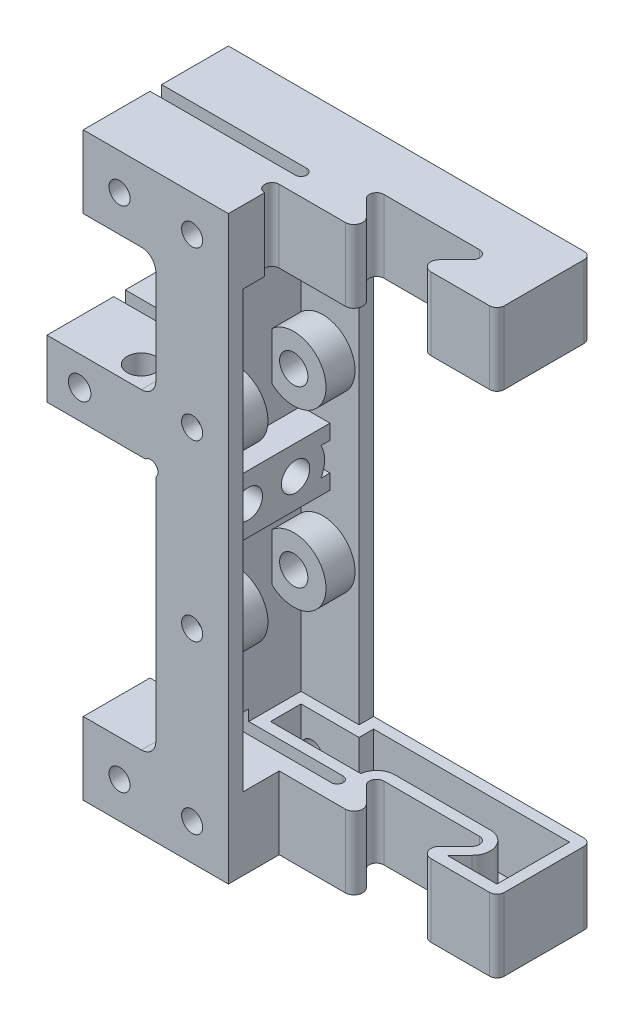
SolidWorks part; units mm, degrees
material "ABS"
ref_plane "Front Plane" through (0, 0, 0) normal (0, 0, 1) x (1, 0, 0)
ref_plane "Top Plane" through (0, 0, 0) normal (0, 1, 0) x (1, 0, 0)
ref_plane "Right Plane" through (0, 0, 0) normal (1, 0, 0) x (0, 0, -1)
sketch "Sketch1" plane through (0, 0, 0) normal (0, 0, 1) x (1, 0, 0)
  line L1 (10, -5) -> (-10, -5)
  line L2 (10, -5) -> (10, 5)
  line L3 (10, 5) -> (-10, 5)
  line L4 (-10, -5) -> (-10, 5)
  line L5 (10, -5) -> (-10, 5) construction
  line L6 (10, 5) -> (-10, -5) construction
  point P0 (0, 0)
  dimension "D1" = 20
  dimension "D2" = 10
extrude "Boss-Extrude1" add sketch "Sketch1" along normal blind 10 and the other way blind 10
hole_wizard "M2.5 Clearance Hole1" positions "Sketch3" profile "Sketch2" hole size "M2.5" standard "DIN" end condition through all
sketch "Sketch3" plane through (0, 0, 10) normal (0, 0, 1) x (1, 0, 0)
  line L7 (0, 0) -> (0, -3.6227) construction
  point P1 (-5, 0)
  point P5 (5, 0)
  dimension "D1" = 10
sketch "Sketch2" plane through (-5, 0, 10) normal (1, 0, 0) x (0, -1, 0)
  line L0 (0, 0) -> (0, 20.0001)
  line L1 (0, 20.0001) -> (1.45, 20.0001)
  line L2 (1.45, 20.0001) -> (1.45, 0)
  line L5 (1.45, 0) -> (0, 0)
  line L11 (0, -6.35) -> (0, 107.95) construction
  dimension "Thru Hole Dia." = 2.9
  dimension "Thru Hole Depth" = 20.0001
sketch "Sketch6" plane through (0, 0, 0) normal (0, 0, 1) x (1, 0, 0)
  line L0 (-10, -5) -> (10, -5) construction
  line L1 (10, -5) -> (0, -5)
  line L2 (10, -5) -> (10, -65)
  line L3 (10, -65) -> (0, -65)
  line L4 (0, -5) -> (0, -65)
  dimension "D1" = 60
extrude "Boss-Extrude2" add sketch "Sketch6" against normal up to surface and the other way up to surface up to face at (-3.55, 0, -10) other way up to face at (-3.55, 0, 10)
ref_plane "Plane1" through (0, -35, 0) normal (0, -1, 0) x (1, 0, 0)
mirror "Mirror1" about plane through (0, -35, 0) normal (0, -1, 0) of "M2.5 Clearance Hole1", "Boss-Extrude1"
sketch "Sketch4" plane through (0, 0, 0) normal (0, 0, 1) x (1, 0, 0)
  line L0 (-10, -5) -> (10, -5)
  line L1 (-10, 5) -> (10, 5)
  line L2 (-10, 5) -> (-10, -5)
  line L3 (-10, -75) -> (10, -75)
  line L4 (10, -75) -> (10, 5) construction
  line L5 (10, -75) -> (-10, -75) construction
  line L6 (-10, -65) -> (10, -65)
  line L7 (-10, -65) -> (-10, -75)
  line L8 (10, 5) -> (10, -5)
  line L9 (10, -75) -> (10, -65)
extrude "Cut-Extrude1" cut sketch "Sketch4" against normal blind 0.8 and the other way blind 0.8
sketch "Sketch7" plane through (0, 0, 0) normal (0, 0, 1) x (1, 0, 0)
  line L0 (0, -5) -> (0, -65) construction
  line L1 (0, -30) -> (-15, -30)
  line L2 (0, -30) -> (0, -22)
  line L3 (0, -22) -> (-15, -22)
  line L4 (-15, -30) -> (-15, -22)
  line L6 (0, -40) -> (-15, -40) construction
  line L7 (0, -40) -> (0, -48) construction
  line L8 (0, -48) -> (-15, -48) construction
  line L9 (-15, -40) -> (-15, -48) construction
  line L10 (-10, -5) -> (0, -5) construction
  dimension "D1" = 10
  dimension "D2" = 25
  dimension "D3" = 8
  dimension "D4" = 15
extrude "Boss-Extrude3" add sketch "Sketch7" along normal up to surface and the other way up to surface up to face at (-3.55, -70, 10) other way up to face at (-3.55, -70, -10)
sketch "Sketch8" plane through (10, 0, 0) normal (1, 0, 0) x (0, 0, -1)
  line L0 (10, 5) -> (-10, -75) construction
  line L1 (8, -65) -> (-8, -65)
  line L2 (8, -65) -> (8, -5)
  line L3 (8, -5) -> (-8, -5)
  line L4 (-8, -65) -> (-8, -5)
  line L5 (8, -65) -> (-8, -5) construction
  line L6 (8, -5) -> (-8, -65) construction
  line L7 (10, 5) -> (0.8, 5) construction
  line L8 (-10, -75) -> (-10, 5) construction
  point P0 (0, -35)
  dimension "D1" = 10
  dimension "D2" = 2
extrude "Cut-Extrude3" cut sketch "Sketch8" against normal blind 8
sketch "Sketch9" plane through (0, 0, 10) normal (0, 0, 1) x (1, 0, 0)
  line L0 (-0.7071, -30.7071) -> (0, -30) construction
  line L1 (-15, -30) -> (0, -30) construction
  line L2 (0, -30) -> (0, -65) construction
  line L3 (0, -30) -> (0, -65) construction
  line L4 (-15, -30) -> (0, -30) construction
  circle A0 centre (-0.7071, -30.7071) radius 1
  dimension "D1" = 2
extrude "Cut-Extrude4" cut sketch "Sketch9" against normal blind 35
fillet "Fillet1" radius 2 5 edges at (0, -22, 0)
sketch "Sketch11" plane through (0, -22, 0) normal (0, 1, 0) x (1, 0, 0)
  line L0 (0, 0) -> (-10, 0) construction
  line L1 (0, 10) -> (0, -10) construction
  line L3 (-5, 0) -> (-5, 7) construction
  circle A0 centre (-5, 7) radius 1.95
  circle A1 centre (-5, -7) radius 1.95
  dimension "D1" = 3.9
  dimension "D2" = 14
  dimension "D3" = 5
extrude "Cut-Extrude6" cut sketch "Sketch11" against normal blind 4
sketch "Sketch12" plane through (0, -22, 0) normal (0, 1, 0) x (1, 0, 0)
  circle A0 centre (-5, 7) radius 1.35
  circle A1 centre (-5, -7) radius 1.35
  dimension "D1" = 2.7
extrude "Cut-Extrude7" cut sketch "Sketch12" against normal blind 9
sketch "Sketch13" plane through (0, 0, 0) normal (-1, 0, 0) x (0, 0, 1)
  line L0 (0, 0) -> (0, -46.5773) construction
  line L1 (-10, -30) -> (10, -30) construction
  circle A0 centre (-3.25, -35) radius 1.35
  circle A1 centre (3.25, -35) radius 1.35
  dimension "D2" = 6.5
  dimension "D3" = 2.7
  dimension "D1" = 5
extrude "Cut-Extrude8" cut sketch "Sketch13" against normal blind 9
sketch "Sketch14" plane through (2, 0, 0) normal (1, 0, 0) x (0, 0, -1)
  circle A0 centre (-3.25, -35) radius 1.95
  circle A1 centre (3.25, -35) radius 1.95 construction
  circle A3 centre (-3.25, -35) radius 4
  dimension "D1" = 3.9
  dimension "D2" = 8
extrude "Boss-Extrude4" add sketch "Sketch14" along normal blind 4
mirror "Mirror2" about plane through (0, 0, 0) normal (0, 0, 1) of "Boss-Extrude4"
sketch "Sketch15" plane through (6, 0, 0) normal (1, 0, 0) x (0, 0, -1)
  line L0 (-8, -5) -> (-8, -65) construction
  line L1 (-8, -31) -> (8, -31)
  line L2 (-8, -31) -> (-8, -33.05)
  line L3 (-8, -33.05) -> (8, -33.05)
  line L4 (8, -31) -> (8, -33.05)
  line L5 (8, -65) -> (8, -5) construction
  line L6 (-3.25, -35) -> (11.9908, -35) construction
  line L7 (8, -39) -> (8, -36.95)
  line L8 (-8, -36.95) -> (8, -36.95)
  line L9 (-8, -39) -> (-8, -36.95)
  line L10 (-8, -39) -> (8, -39)
  circle A0 centre (3.25, -35) radius 1.95 construction
  arc A1 (0, -32.6682) -> (0, -37.3318) centre (-3.25, -35) ccw construction
extrude "Boss-Extrude5" add sketch "Sketch15" against normal up to surface (4 mm away) up to face at (2, -35, 0)
hole_wizard "M2.5 Clearance Hole2" positions "Sketch17" profile "Sketch16" hole size "M2.5" standard "DIN"
sketch "Sketch17" plane through (0, 0, -10) normal (0, 0, -1) x (-1, 0, 0)
  line L0 (-5, 0) -> (-5, -23) construction
  line L2 (-10, -35) -> (-30.659, -35) construction
  line L3 (-10, -75) -> (-10, 5) construction
  point P0 (-5, -23)
  point P17 (-5, -47)
  dimension "D1" = 23
sketch "Sketch16" plane through (5, -23, -10) normal (1, 0, 0) x (0, 1, 0)
  line L0 (0, 0) -> (0, 20)
  line L1 (0, 20) -> (1.45, 20)
  line L2 (1.45, 20) -> (1.45, 0)
  line L5 (1.45, 0) -> (0, 0)
  line L10 (0, 20) -> (-1.45, 20) construction
  line L11 (0, -6.35) -> (0, 107.95) construction
  dimension "Hole Dia." = 2.9
  dimension "Hole Depth" = 20
  dimension "Drill Angle" = 180
sketch "Sketch19" plane through (0, 0, 8) normal (0, 0, -1) x (-1, 0, 0)
  circle A0 centre (-5, -23) radius 1.95
  circle A1 centre (-5, -23) radius 4.45
  dimension "D1" = 3.9
  dimension "D2" = 2.5
extrude "Boss-Extrude6" add sketch "Sketch19" along normal blind 4
mirror "Mirror3" about plane through (0, 0, 0) normal (0, 0, 1) of "Boss-Extrude6"
ref_plane "Plane2" through (0, -35, 0) normal (0, 1, 0) x (-1, 0, 0)
mirror "Mirror4" about plane through (0, -35, 0) normal (0, 1, 0) of "Mirror3", "Boss-Extrude6"
sketch "Sketch20" plane through (0, 5, 0) normal (0, 1, 0) x (1, 0, 0)
  line L1 (-29.6046, 0.8) -> (0, 0.8)
  line L2 (-29.6046, 0.8) -> (-29.6046, -0.8)
  line L3 (-29.6046, -0.8) -> (0, -0.8)
  line L4 (0, 0.8) -> (0, -0.8)
  line L5 (10, -0.8) -> (-10, -0.8) construction
extrude "Cut-Extrude9" cut sketch "Sketch20" against normal blind 128
hole_wizard "M2.5 Clearance Hole3" positions "Sketch22" profile "Sketch23" hole size "M2.5" standard "DIN" end condition through all
sketch "Sketch22" plane through (0, 0, 10) normal (0, 0, 1) x (1, 0, 0)
  line L0 (-15, -26) -> (14.615, -26) construction
  line L1 (-15, -22) -> (-15, -30) construction
  point P0 (-10.5, -26)
  dimension "D1" = 4.5
sketch "Sketch23" plane through (-10.5, -26, 10) normal (1, 0, 0) x (0, -1, 0)
  line L0 (0, 0) -> (0, 20)
  line L1 (0, 20) -> (1.55, 20)
  line L2 (1.55, 20) -> (1.55, 0)
  line L5 (1.55, 0) -> (0, 0)
  line L11 (0, -6.35) -> (0, 107.95) construction
  dimension "Thru Hole Dia." = 3.1
  dimension "Thru Hole Depth" = 20
sketch "Sketch24" plane through (0, 0, 0) normal (-1, 0, 0) x (0, 0, 1)
  line L0 (-0.8, -5) -> (0.8, -5) construction
  line L1 (-0.8, -5) -> (0.8, -5)
  line L2 (-0.8, -5) -> (-0.8, -6.5)
  line L3 (-0.8, -6.5) -> (0.8, -6.5)
  line L4 (0.8, -5) -> (0.8, -6.5)
  line L5 (0.8, -7) -> (0.8, -5) construction
  line L6 (-0.8, -5) -> (-0.8, -7) construction
  line L7 (-10, 5) -> (-10, -75) construction
  line L8 (-10, -35) -> (15.2028, -35) construction
  line L9 (0.8, -65) -> (0.8, -63.5)
  line L10 (-0.8, -63.5) -> (0.8, -63.5)
  line L11 (-0.8, -65) -> (-0.8, -63.5)
  line L12 (-0.8, -65) -> (0.8, -65)
  dimension "D1" = 1.5
extrude "Cut-Extrude10" cut sketch "Sketch24" against normal blind 20
sketch "Sketch25" plane through (0, 5, 0) normal (0, 1, 0) x (1, 0, 0)
  line L0 (10, 10) -> (40, 10)
  line L1 (40, 10) -> (40, -3)
  line L2 (10, 10) -> (10, -3)
  line L3 (10, -3) -> (22, -3)
  line L4 (22, -3) -> (16, 3)
  line L5 (16, 3) -> (34, 3)
  line L6 (28, -3) -> (34, 3)
  line L7 (28, -3) -> (40, -3)
  line L8 (20.7373, 10) -> (40, 10) construction
  line L10 (10, 10) -> (10, 14.9089) construction
  line L11 (10, 10) -> (-10, 10) construction
  line L12 (10, 10) -> (10, 0.8) construction
  dimension "D1" = 45
extrude "Boss-Extrude7" add sketch "Sketch25" against normal blind 10
fillet "Fillet2" radius 1 4 edges at (34, 0, -3) (16, 0, -3) (40, 0, -10) (40, 0, 3)
fillet "Fillet3" radius 1.2 2 edges at (28, 0, 3) (22, 0, 3)
sketch "Sketch27" plane through (0, 5, 0) normal (0, 1, 0) x (1, 0, 0)
  line L0 (10, 0.8) -> (10, -0.8) construction
  line L1 (10, -3) -> (10, -10) construction
  circle A0 centre (10, 0) radius 0.8
  circle A1 centre (10, -4) radius 1
  dimension "D1" = 2
extrude "Cut-Extrude11" cut sketch "Sketch27" against normal blind 10
sketch "Sketch28" plane through (0, -5, 0) normal (0, -1, 0) x (1, 0, 0)
  line L0 (18.3787, 1.5) -> (11.7436, 1.5)
  line L1 (19.1029, 3) -> (10, 3) construction
  line L2 (18.3787, 1.5) -> (10, 1.5) construction
  line L5 (10, -2.3) -> (3.5, -2.3)
  line L6 (3.5, -2.3) -> (3.5, -6.5)
  line L7 (3.5, -6.5) -> (11.5, -6.5)
  line L8 (11.5, -6.5) -> (11.5, -8.5)
  line L9 (11.5, -8.5) -> (38.5, -8.5)
  line L10 (38.5, -8.5) -> (38.5, 1.5)
  line L11 (38.5, 1.5) -> (31.6213, 1.5)
  line L12 (31.6213, 1.5) -> (33.3536, -0.2322)
  line L13 (31.5858, -4.5) -> (18.4142, -4.5)
  line L14 (16.6464, -0.2322) -> (18.3787, 1.5)
  line L15 (19.1029, 3) -> (10, 3)
  line L16 (10, 5) -> (10, 8)
  line L17 (10, 8) -> (2, 8)
  line L18 (2, 8) -> (2, 0.8)
  line L19 (2, 0.8) -> (10, 0.8)
  line L20 (10, -0.8) -> (2, -0.8)
  line L21 (2, -0.8) -> (2, -8)
  line L22 (2, -8) -> (10, -8)
  line L23 (10, -8) -> (10, -10)
  line L24 (10, -10) -> (39, -10)
  line L25 (40, -9) -> (40, 2)
  line L26 (39, 3) -> (30.8971, 3)
  line L27 (30.0485, 0.9515) -> (32.2929, -1.2929)
  line L28 (31.5858, -3) -> (18.4142, -3)
  line L29 (17.7071, -1.2929) -> (19.9515, 0.9515)
  line L30 (19.1029, 3) -> (11.0887, 3) construction
  line L33 (2, 8) -> (2, 0.8) construction
  line L34 (2, 0.8) -> (10, 0.8) construction
  line L35 (10, -0.8) -> (2, -0.8) construction
  line L36 (2, -0.8) -> (2, -8) construction
  line L37 (2, -8) -> (10, -8) construction
  line L38 (10, -8) -> (10, -10) construction
  line L39 (10, -10) -> (39, -10) construction
  line L40 (40, -9) -> (40, 2) construction
  line L41 (39, 3) -> (30.8971, 3) construction
  line L42 (30.0485, 0.9515) -> (32.2929, -1.2929) construction
  line L43 (31.5858, -3) -> (18.4142, -3) construction
  line L44 (17.7071, -1.2929) -> (19.9515, 0.9515) construction
  line L45 (8.5, 6) -> (8.5, 6.5) construction
  line L46 (8.5, 6.5) -> (3.5, 6.5) construction
  line L47 (3.5, 6.5) -> (3.5, 2.3) construction
  line L48 (3.5, 2.3) -> (10, 2.3) construction
  line L49 (10, 5) -> (10, 8) construction
  line L50 (10, 8) -> (2, 8) construction
  arc A0 (10, -2.3) -> (10, 2.3) centre (10, 0) ccw construction
  arc A1 (10, -2.3) -> (11.7436, 1.5) centre (10, 0) ccw
  arc A2 (38.5, -8.5) -> (38.5, -8.5) centre (38.5, -8.5) ccw
  arc A3 (38.5, 1.5) -> (38.5, 1.5) centre (38.5, 1.5) ccw
  arc A4 (31.6213, 1.5) -> (31.6213, 1.5) centre (31.6213, 1.5) ccw
  arc A5 (31.5858, -4.5) -> (33.3536, -0.2322) centre (31.5858, -2) ccw
  arc A6 (16.6464, -0.2322) -> (18.4142, -4.5) centre (18.4142, -2) ccw
  arc A7 (18.3787, 1.5) -> (18.3787, 1.5) centre (18.3787, 1.5) ccw
  arc A8 (10, 5) -> (10, 3) centre (10, 4) ccw
  arc A9 (10, -0.8) -> (10, 0.8) centre (10, 0) ccw
  arc A10 (39, -10) -> (40, -9) centre (39, -9) ccw
  arc A11 (40, 2) -> (39, 3) centre (39, 2) ccw
  arc A12 (30.8971, 3) -> (30.0485, 0.9515) centre (30.8971, 1.8) ccw
  arc A13 (31.5858, -3) -> (32.2929, -1.2929) centre (31.5858, -2) ccw
  arc A14 (17.7071, -1.2929) -> (18.4142, -3) centre (18.4142, -2) ccw
  arc A17 (10, -0.8) -> (10, 0.8) centre (10, 0) ccw construction
  arc A18 (39, -10) -> (40, -9) centre (39, -9) ccw construction
  arc A19 (40, 2) -> (39, 3) centre (39, 2) ccw construction
  arc A20 (19.9515, 0.9515) -> (19.1029, 3) centre (19.1029, 1.8) ccw
  arc A21 (31.5858, -3) -> (32.2929, -1.2929) centre (31.5858, -2) ccw construction
  arc A22 (17.7071, -1.2929) -> (18.4142, -3) centre (18.4142, -2) ccw construction
  arc A24 (8.5, 6) -> (10, 1.5) centre (10, 4) ccw construction
  arc A25 (10, 5) -> (10, 3) centre (10, 4) ccw construction
  arc A33 (30.8971, 3) -> (30.0485, 0.9515) centre (30.5314, 1.9515) ccw construction
  arc A34 (19.9515, 0.9515) -> (19.1029, 3) centre (19.4686, 1.9515) ccw construction
  dimension "D1" = 0
  dimension "D2" = 1.5
extrude "Cut-Extrude12" cut sketch "Sketch28" against normal blind 8.5
ref_plane "Plane3" through (0, -35, 0) normal (0, 1, 0) x (-1, 0, 0)
mirror "Mirror5" about plane through (0, -35, 0) normal (0, 1, 0) of "Fillet3", "Fillet2", "Boss-Extrude7"
sketch "Sketch30" plane through (0, -75, 0) normal (0, -1, 0) x (1, 0, 0)
  line L1 (15, 0.8) -> (10, 0.8)
  line L2 (15, 0.8) -> (15, -0.8)
  line L3 (15, -0.8) -> (10, -0.8)
  line L4 (10, 0.8) -> (10, -0.8)
  line L5 (15, 0.8) -> (10, -0.8) construction
  line L6 (15, -0.8) -> (10, 0.8) construction
  point P0 (12.5, 0)
  dimension "D1" = 5
extrude "Cut-Extrude13" cut sketch "Sketch30" against normal blind 10.5
sketch "Sketch31" plane through (0, -75, 0) normal (0, -1, 0) x (1, 0, 0)
  line L0 (15, -0.8) -> (15, 0.8) construction
  line L1 (-10, 0.8) -> (15, 0.8) construction
  circle A0 centre (15, 0) radius 0.8
extrude "Cut-Extrude14" cut sketch "Sketch31" against normal blind 10
sketch "Sketch32" plane through (0, -65, 0) normal (0, 1, 0) x (1, 0, 0)
  line L0 (3.5, 2.3) -> (15.9323, 2.3)
  line L2 (18.4142, 4.5) -> (31.5858, 4.5)
  line L3 (33.3536, 0.2322) -> (31.6213, -1.5)
  line L4 (31.6213, -1.5) -> (38.5, -1.5)
  line L5 (38.5, -1.5) -> (38.5, 8.5)
  line L6 (38.5, 8.5) -> (11.5, 8.5)
  line L7 (11.5, 8.5) -> (11.5, 6.5)
  line L8 (11.5, 6.5) -> (3.5, 6.5)
  line L9 (3.5, 6.5) -> (3.5, 2.3)
  line L15 (2, 0.8) -> (15, 0.8)
  line L16 (15, -0.8) -> (2, -0.8)
  line L17 (2, -0.8) -> (2, -8)
  line L18 (2, -8) -> (10, -8)
  line L19 (10, -8) -> (10, -3)
  line L20 (10, -3) -> (19.1029, -3)
  line L21 (19.9515, -0.9515) -> (17.7071, 1.2929)
  line L22 (18.4142, 3) -> (31.5858, 3)
  line L23 (32.2929, 1.2929) -> (30.0485, -0.9515)
  line L24 (30.8971, -3) -> (39, -3)
  line L25 (40, -2) -> (40, 9)
  line L26 (39, 10) -> (10, 10)
  line L27 (10, 10) -> (10, 8)
  line L28 (10, 8) -> (2, 8)
  line L29 (2, 8) -> (2, 0.8)
  line L30 (2, 0.8) -> (18.2, 0.8) construction
  line L36 (18.2, 0.8) -> (17.7071, 1.2929) construction
  line L37 (18.4142, 3) -> (31.5858, 3) construction
  line L38 (32.2929, 1.2929) -> (30.0485, -0.9515) construction
  line L39 (30.8971, -3) -> (39, -3) construction
  line L40 (40, -2) -> (40, 9) construction
  line L41 (39, 10) -> (10, 10) construction
  line L42 (10, 10) -> (10, 8) construction
  line L43 (10, 8) -> (2, 8) construction
  line L44 (2, 8) -> (2, 0.8) construction
  arc A0 (18.4142, 4.5) -> (15.9323, 2.3) centre (18.4142, 2) ccw
  arc A1 (33.3536, 0.2322) -> (31.5858, 4.5) centre (31.5858, 2) ccw
  arc A7 (15, -0.8) -> (15, 0.8) centre (15, 0) ccw
  arc A9 (18.4142, 3) -> (17.7071, 1.2929) centre (18.4142, 2) ccw
  arc A10 (32.2929, 1.2929) -> (31.5858, 3) centre (31.5858, 2) ccw
  arc A12 (39, -3) -> (40, -2) centre (39, -2) ccw
  arc A13 (40, 9) -> (39, 10) centre (39, 9) ccw
  arc A14 (19.1029, -3) -> (19.9515, -0.9515) centre (19.1029, -1.8) ccw
  arc A16 (18.4142, 3) -> (17.7071, 1.2929) centre (18.4142, 2) ccw construction
  arc A17 (32.2929, 1.2929) -> (31.5858, 3) centre (31.5858, 2) ccw construction
  arc A18 (30.0485, -0.9515) -> (30.8971, -3) centre (30.8971, -1.8) ccw
  arc A19 (39, -3) -> (40, -2) centre (39, -2) ccw construction
  arc A20 (40, 9) -> (39, 10) centre (39, 9) ccw construction
  dimension "D1" = 0
extrude "Cut-Extrude15" cut sketch "Sketch32" against normal blind 8.5
